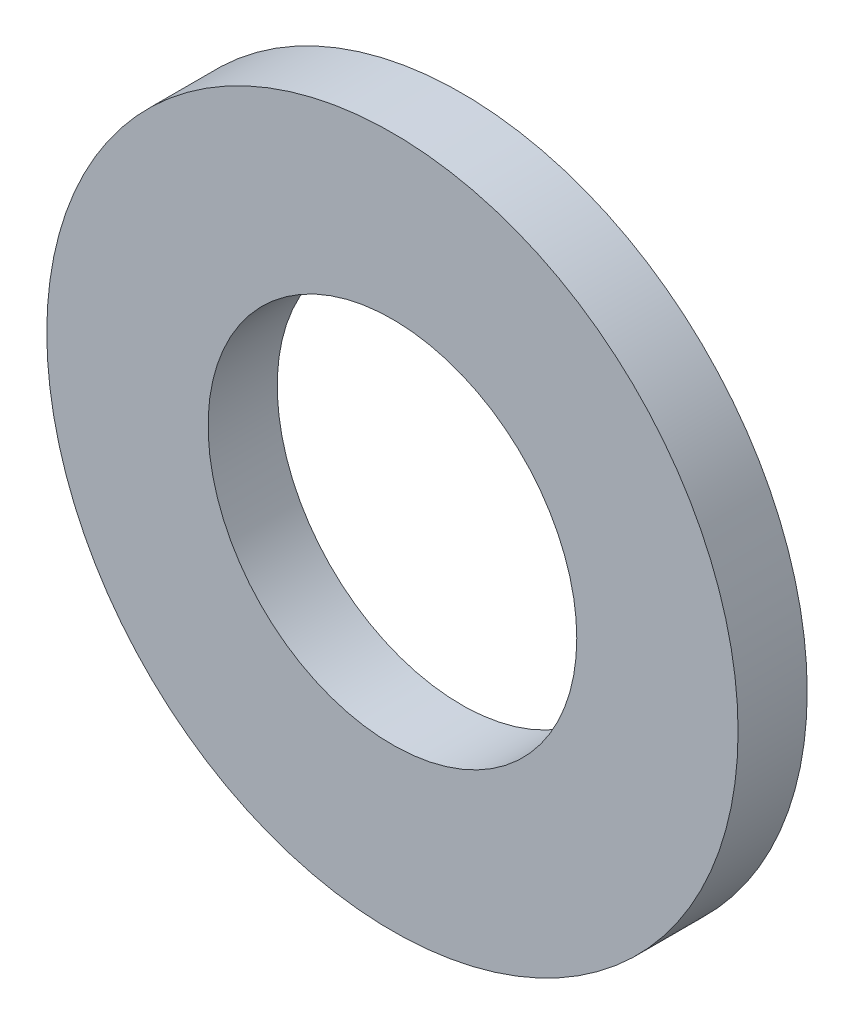
SolidWorks part; units mm, degrees
note: '?' marks a value the reader was unsure of.
ref_plane "Front Plane" through (0, 0, 0) normal (0, 0, 1) x (1, 0, 0)
ref_plane "Top Plane" through (0, 0, 0) normal (0, 1, 0) x (1, 0, 0)
ref_plane "Right Plane" through (0, 0, 0) normal (1, 0, 0) x (0, 0, -1)
sketch "Sketch1" plane through (0, 0, 0) normal (0, 0, 1) x (1, 0, 0)
  circle A0 centre (0, 0) radius 3
  circle A1 centre (0, 0) radius 1.6
  dimension "OD" = 6
  dimension "ID1" = 3.2
extrude "Boss-Extrude1" add sketch "Sketch1" along normal blind 0.6
ref_axis "Center Axis 1" through (0, 0, 0.6) along (0, 0, -1)?
ref_plane "Contact Plane 1" through (0, 0, 0.6) normal (0, 0, 1) x (1, 0, 0)
ref_plane "Contact Plane 2" through (0, 0, 0) normal (0, 0, -1) x (-1, 0, 0)
